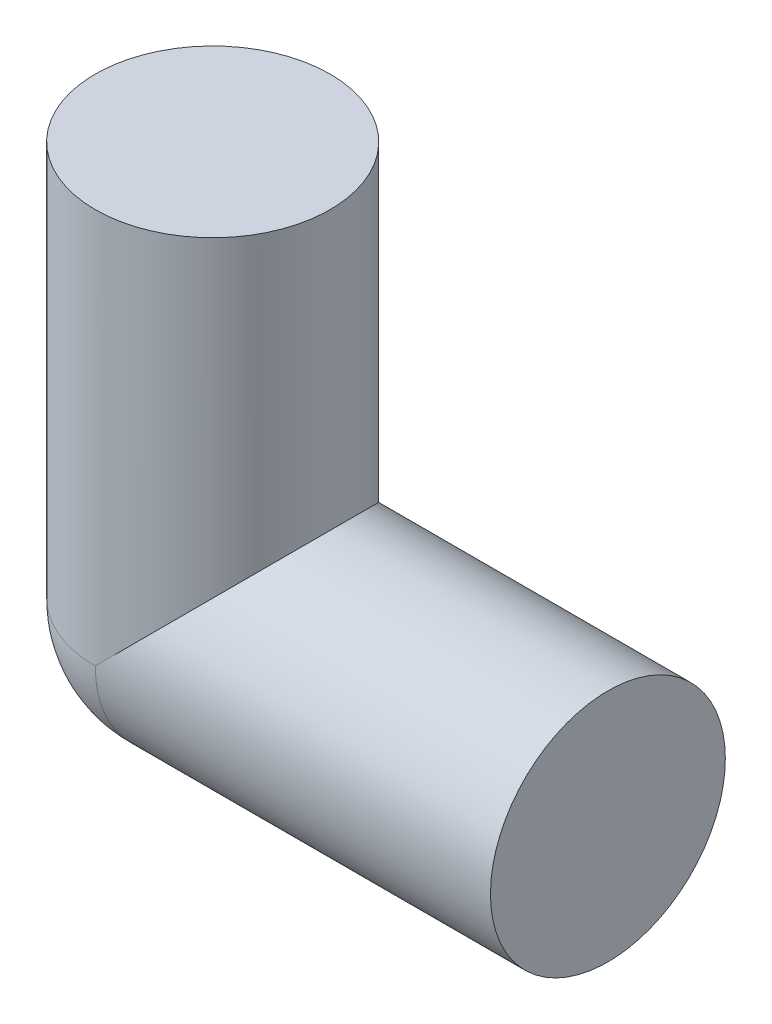
SolidWorks part; units mm, degrees
material "Brass"
ref_plane "Front Plane" through (0, 0, 0) normal (0, 0, 1) x (1, 0, 0)
ref_plane "Top Plane" through (0, 0, 0) normal (0, 1, 0) x (1, 0, 0)
ref_plane "Right Plane" through (0, 0, 0) normal (1, 0, 0) x (0, 0, -1)
sketch "Sketch1" plane through (0, 0, 0) normal (0, 1, 0) x (1, 0, 0)
  circle A0 centre (0, 0) radius 8
  dimension "D1" = 16
extrude "Boss-Extrude1" add sketch "Sketch1" along normal blind 26.924
sketch "Sketch2" plane through (0, 0, 0) normal (1, 0, 0) x (0, 0, -1)
  circle A0 centre (0, 0) radius 8
extrude "Boss-Extrude2" add sketch "Sketch2" along normal blind 26.924
sketch "Sketch3" plane through (0, 0, 0) normal (-1, 0, 0) x (0, 0, 1)
  line L0 (-8, 0) -> (8, 0)
  line L1 (0, 0) -> (12.5512, 0) construction
  arc A0 (-8, 0) -> (8, 0) centre (0, 0) ccw
revolve "Revolve1" add sketch "Sketch3" angle 90 about L1 reverse direction yes
